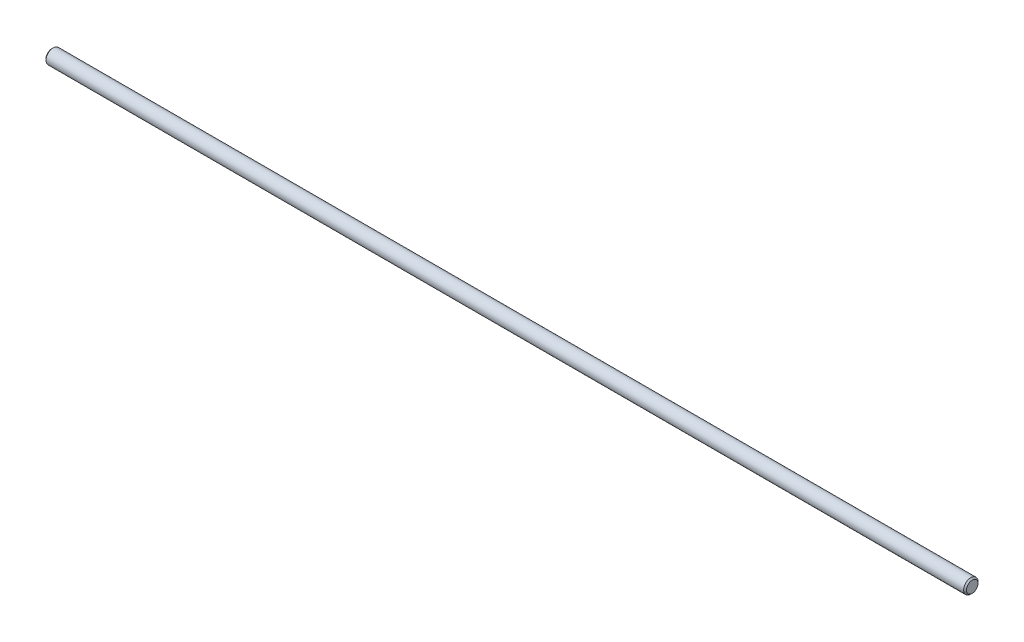
SolidWorks part; units mm, degrees
ref_plane "Front" through (0, 0, 0) normal (0, 0, 1) x (1, 0, 0)
ref_plane "Top" through (0, 0, 0) normal (0, 1, 0) x (1, 0, 0)
ref_plane "Right" through (0, 0, 0) normal (1, 0, 0) x (0, 0, -1)
sketch "Sketch1" plane through (0, 0, 0) normal (0, 0, 1) x (1, 0, 0)
  line L0 (-203.2, 0) -> (203.2, 0) construction
  line L1 (203.2, 3.175) -> (203.2, -3.175) construction
  line L2 (-203.2, 3.175) -> (-203.2, -3.175) construction
  dimension "Length" = 406.4
  dimension "Diameter" = 6.35
sketch "Sketch2" plane through (0, 0, 0) normal (1, 0, 0) x (0, 0, -1)
  circle A0 centre (0, 0) radius 3.175
extrude "Extrude1" add sketch "Sketch2" against normal up to vertex (203.2 mm away) and the other way up to vertex (203.2 mm away) up to point (-203.2, 3.175, 0) other way up to point (203.2, 3.175, 0)
chamfer "Chamfer1" distance 0.635 angle 45 2 edges at (203.2, 0, -3.175) (-203.2, 0, -3.175)
equation "\"D1@Chamfer1\" = \"Diameter@Sketch1\"*.1"
